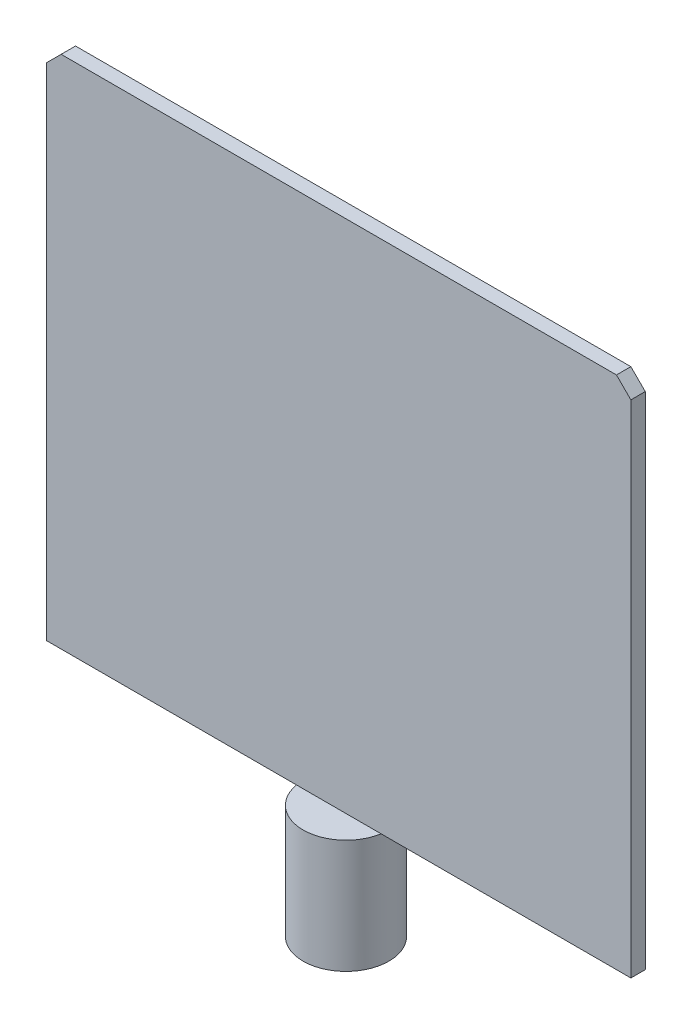
SolidWorks part; units mm, degrees
ref_plane "Plan de face" through (0, 0, 0) normal (0, 0, 1) x (1, 0, 0)
ref_plane "Plan de dessus" through (0, 0, 0) normal (0, 1, 0) x (1, 0, 0)
ref_plane "Plan de droite" through (0, 0, 0) normal (1, 0, 0) x (0, 0, -1)
sketch "Esquisse2" plane through (0, 0, 0) normal (0, 1, 0) x (1, 0, 0)
  circle A0 centre (0, 0) radius 2.98
  dimension "D1" = 5.96
extrude "Boss.-Extru.1" add sketch "Esquisse2" against normal blind 7.9
sketch "Esquisse3" plane through (0, 0, 0) normal (0, 0, 1) x (1, 0, 0)
  line L0 (2.98, 0) -> (-2.98, 0) construction
  line L1 (-20.3, 35.8) -> (20.3, 35.8)
  line L2 (-20.3, 35.8) -> (-20.3, 0)
  line L3 (-20.3, 0) -> (20.3, 0)
  line L4 (20.3, 35.8) -> (20.3, 0)
  line L8 (-2.98, -7.9) -> (2.98, -7.9) construction
  point P6 (0, 35.8)
  dimension "D1" = 40.6
  dimension "D2" = 43.7
extrude "Boss.-Extru.2" add sketch "Esquisse3" along normal blind 0.5 and the other way blind 0.5
chamfer "Chanfrein1" distance 1 angle 45 2 edges at (-20.3, 35.8, 0) (20.3, 35.8, 0)
